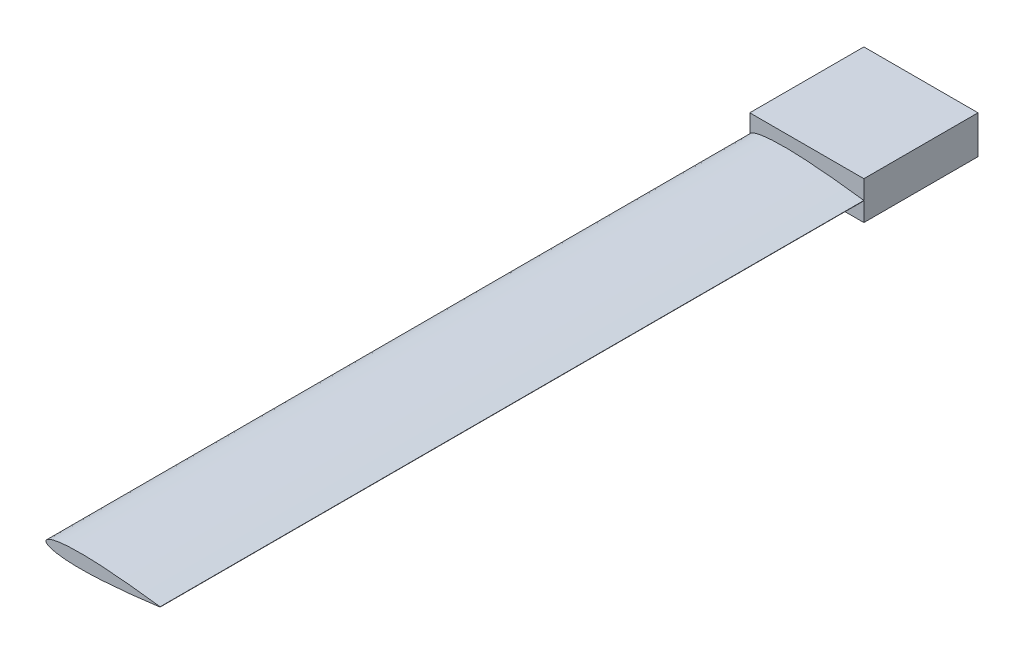
SolidWorks part; units mm, degrees
ref_plane "Front Plane" through (0, 0, 0) normal (0, 0, 1) x (1, 0, 0)
ref_plane "Top Plane" through (0, 0, 0) normal (0, 1, 0) x (1, 0, 0)
ref_plane "Right Plane" through (0, 0, 0) normal (1, 0, 0) x (0, 0, -1)
curve "Curve1"
  spline degree 3 poles (25.4, 0.032, 0) (25.3951, 0.0327, 0) (25.3753, 0.0355, 0) (25.3309, 0.0417, 0) (25.257, 0.052, 0) (25.1537, 0.0664, 0) (25.0214, 0.0846, 0) (24.8603, 0.1068, 0) (24.6708, 0.1326, 0) (24.4533, 0.1619, 0) (24.2084, 0.1946, 0) (23.9366, 0.2304, 0) (23.6385, 0.2691, 0) (23.3149, 0.3106, 0) (22.9666, 0.3545, 0) (22.5942, 0.4008, 0) (22.1987, 0.449, 0) (21.7811, 0.499, 0) (21.3422, 0.5505, 0) (20.8832, 0.6032, 0) (20.405, 0.6571, 0) (19.9089, 0.7116, 0) (19.3959, 0.7667, 0) (18.8673, 0.8219, 0) (18.3242, 0.8772, 0) (17.7681, 0.9321, 0) (17.2001, 0.9864, 0) (16.6216, 1.0399, 0) (16.0339, 1.0922, 0) (15.4384, 1.143, 0) (14.8366, 1.1921, 0) (14.2297, 1.2391, 0) (13.6193, 1.2836, 0) (13.0067, 1.3254, 0) (12.3935, 1.3642, 0) (11.7809, 1.3995, 0) (11.1705, 1.4311, 0) (10.5636, 1.4587, 0) (9.9618, 1.4818, 0) (9.3663, 1.5004, 0) (8.7786, 1.514, 0) (8.2001, 1.5224, 0) (7.632, 1.5254, 0) (7.0758, 1.5227, 0) (6.5327, 1.5144, 0) (6.0041, 1.5, 0) (5.491, 1.4798, 0) (4.9948, 1.4535, 0) (4.5166, 1.4212, 0) (4.0575, 1.3829, 0) (3.6185, 1.3388, 0) (3.2008, 1.2888, 0) (2.8052, 1.2334, 0) (2.4327, 1.1725, 0) (2.0841, 1.1064, 0) (1.7603, 1.0355, 0) (1.462, 0.96, 0) (1.1898, 0.8801, 0) (0.9445, 0.7962, 0) (0.7264, 0.7086, 0) (0.536, 0.6175, 0) (0.3737, 0.523, 0) (0.2396, 0.4254, 0) (0.1341, 0.3245, 0) (0.0574, 0.22, 0) (0.0105, 0.1114, 0) (-0.0051, 0, 0) (0.0105, -0.1114, 0) (0.0574, -0.22, 0) (0.1341, -0.3245, 0) (0.2396, -0.4254, 0) (0.3737, -0.523, 0) (0.536, -0.6175, 0) (0.7264, -0.7086, 0) (0.9445, -0.7962, 0) (1.1898, -0.8801, 0) (1.462, -0.96, 0) (1.7603, -1.0355, 0) (2.0841, -1.1064, 0) (2.4327, -1.1725, 0) (2.8052, -1.2334, 0) (3.2008, -1.2888, 0) (3.6185, -1.3388, 0) (4.0575, -1.3829, 0) (4.5166, -1.4212, 0) (4.9948, -1.4535, 0) (5.491, -1.4798, 0) (6.0041, -1.5, 0) (6.5327, -1.5144, 0) (7.0758, -1.5227, 0) (7.632, -1.5254, 0) (8.2001, -1.5224, 0) (8.7786, -1.514, 0) (9.3663, -1.5004, 0) (9.9618, -1.4818, 0) (10.5636, -1.4587, 0) (11.1705, -1.4311, 0) (11.7809, -1.3995, 0) (12.3935, -1.3642, 0) (13.0067, -1.3254, 0) (13.6193, -1.2836, 0) (14.2297, -1.2391, 0) (14.8366, -1.1921, 0) (15.4384, -1.143, 0) (16.0339, -1.0922, 0) (16.6216, -1.0399, 0) (17.2001, -0.9864, 0) (17.7681, -0.9321, 0) (18.3242, -0.8772, 0) (18.8673, -0.8219, 0) (19.3959, -0.7667, 0) (19.9089, -0.7116, 0) (20.405, -0.6571, 0) (20.8832, -0.6032, 0) (21.3422, -0.5505, 0) (21.7811, -0.499, 0) (22.1987, -0.449, 0) (22.5942, -0.4008, 0) (22.9666, -0.3545, 0) (23.3149, -0.3106, 0) (23.6385, -0.2691, 0) (23.9366, -0.2304, 0) (24.2084, -0.1946, 0) (24.4533, -0.1619, 0) (24.6708, -0.1326, 0) (24.8603, -0.1068, 0) (25.0214, -0.0846, 0) (25.1537, -0.0664, 0) (25.257, -0.052, 0) (25.3309, -0.0417, 0) (25.3753, -0.0355, 0) (25.3951, -0.0327, 0) (25.4, -0.032, 0) knots 0 0 0 0 0.000289 0.001156 0.002598 0.004612 0.007194 0.010336 0.014031 0.018272 0.023046 0.028343 0.03415 0.040454 0.047238 0.054489 0.062187 0.070314 0.078852 0.08778 0.097078 0.106722 0.116691 0.126961 0.137507 0.148306 0.159331 0.170556 0.181957 0.193504 0.205171 0.216932 0.228758 0.240621 0.252495 0.26435 0.276161 0.287898 0.299536 0.311047 0.322405 0.333584 0.344559 0.355306 0.3658 0.376018 0.385937 0.395538 0.404798 0.413699 0.422221 0.430349 0.438066 0.445357 0.452209 0.458612 0.464554 0.47003 0.475035 0.479569 0.483637 0.48725 0.490431 0.493219 0.495674 0.497891 0.5 0.502109 0.504326 0.506781 0.509569 0.51275 0.516363 0.520431 0.524965 0.52997 0.535446 0.541388 0.547791 0.554643 0.561934 0.569651 0.577779 0.586301 0.595202 0.604462 0.614063 0.623982 0.6342 0.644694 0.655441 0.666416 0.677595 0.688953 0.700464 0.712102 0.723839 0.73565 0.747505 0.759379 0.771242 0.783068 0.794829 0.806496 0.818043 0.829444 0.840669 0.851694 0.862493 0.873039 0.883309 0.893278 0.902922 0.91222 0.921148 0.929686 0.937813 0.945511 0.952762 0.959546 0.96585 0.971657 0.976954 0.981728 0.985969 0.989664 0.992806 0.995388 0.997402 0.998844 0.999711 1 1 1 1
sketch "Sketch2" plane through (0, 0, 0) normal (0, 0, 1) x (1, 0, 0)
  line L0 (25.2718, 0.0377) -> (25.2718, -0.0379)
  line L1 (25.2718, -0.0001) -> (-4.7282, -0.0001) construction
  line L2 (-4.7282, -0.0001) -> (-4.7282, 9.0074) construction
  spline S1 degree 3 poles (25.2718, 0.0377) (25.2659, 0.0385) (25.2426, 0.0418) (25.1495, 0.0548) (25.01, 0.0743) (24.8246, 0.0999) (24.6343, 0.1261) (24.4105, 0.1565) (24.1536, 0.1911) (23.8643, 0.2297) (23.5433, 0.272) (23.1913, 0.3178) (22.8091, 0.3667) (22.2419, 0.4383) (21.6376, 0.5126) (20.9975, 0.5892) (20.4792, 0.6501) (19.937, 0.7124) (19.3722, 0.776) (18.7862, 0.8404) (18.1803, 0.9054) (17.556, 0.9706) (16.9146, 1.0359) (16.2577, 1.1008) (15.5868, 1.165) (14.9036, 1.2281) (14.2094, 1.29) (13.5061, 1.35) (12.7953, 1.4079) (12.0785, 1.4634) (11.3576, 1.516) (10.6341, 1.5654) (9.9097, 1.6112) (8.9473, 1.6667) (7.9892, 1.7135) (6.8062, 1.759) (5.8749, 1.7847) (4.9569, 1.798) (4.286, 1.8015) (3.6291, 1.7984) (2.9876, 1.7886) (2.3632, 1.7716) (1.7573, 1.7477) (1.1712, 1.7166) (0.6064, 1.6785) (0.0641, 1.6333) (-0.4544, 1.5811) (-0.9478, 1.5222) (-1.415, 1.4567) (-1.855, 1.3847) (-2.2666, 1.3067) (-2.6491, 1.223) (-3.0014, 1.1338) (-3.3229, 1.0394) (-3.6127, 0.9404) (-3.8703, 0.8368) (-4.0952, 0.7292) (-4.2869, 0.6176) (-4.4452, 0.5024) (-4.5698, 0.3832) (-4.6604, 0.2598) (-4.7158, 0.1315) (-4.7342, -0.0001) (-4.7158, -0.1317) (-4.6604, -0.2599) (-4.5698, -0.3834) (-4.4452, -0.5025) (-4.2869, -0.6178) (-4.0952, -0.7294) (-3.8703, -0.837) (-3.6127, -0.9405) (-3.3229, -1.0396) (-3.0014, -1.1339) (-2.6491, -1.2232) (-2.2666, -1.3069) (-1.855, -1.3849) (-1.415, -1.4568) (-0.9478, -1.5223) (-0.4544, -1.5813) (0.0641, -1.6335) (0.6064, -1.6787) (1.1712, -1.7168) (1.7573, -1.7479) (2.3632, -1.7718) (2.9876, -1.7887) (3.6291, -1.7986) (4.286, -1.8017) (4.9569, -1.7982) (5.8749, -1.7848) (7.0455, -1.7526) (8.2283, -1.7026) (9.1862, -1.653) (9.9097, -1.6113) (10.6341, -1.5656) (11.3576, -1.5162) (12.0785, -1.4636) (12.7953, -1.4081) (13.5061, -1.3501) (14.2094, -1.2901) (14.9036, -1.2283) (15.5868, -1.1652) (16.2577, -1.101) (16.9146, -1.0361) (17.556, -0.9708) (18.1803, -0.9056) (18.7862, -0.8405) (19.3722, -0.7761) (19.937, -0.7126) (20.4792, -0.6503) (20.9975, -0.5894) (21.6376, -0.5128) (22.2419, -0.4385) (22.8091, -0.3669) (23.1913, -0.318) (23.5433, -0.2722) (23.8643, -0.2299) (24.1536, -0.1913) (24.4105, -0.1567) (24.6343, -0.1262) (24.8246, -0.1001) (25.01, -0.0745) (25.1495, -0.055) (25.2426, -0.042) (25.2659, -0.0387) (25.2718, -0.0379) knots 0 0 0 0 0.000289 0.001156 0.004612 0.007194 0.010336 0.014031 0.018272 0.023046 0.028343 0.03415 0.040454 0.047238 0.062187 0.070314 0.078852 0.08778 0.097078 0.106722 0.116691 0.126961 0.137507 0.148306 0.159331 0.170556 0.181957 0.193504 0.205171 0.216932 0.228758 0.240621 0.252495 0.26435 0.287898 0.299536 0.322405 0.333584 0.344559 0.355306 0.3658 0.376018 0.385937 0.395538 0.404798 0.413699 0.422221 0.430349 0.438066 0.445357 0.452209 0.458612 0.464554 0.47003 0.475035 0.479569 0.483637 0.48725 0.490431 0.493219 0.495674 0.497891 0.5 0.502109 0.504326 0.506781 0.509569 0.51275 0.516363 0.520431 0.524965 0.52997 0.535446 0.541388 0.547791 0.554643 0.561934 0.569651 0.577779 0.586301 0.595202 0.604462 0.614063 0.623982 0.6342 0.644694 0.655441 0.666416 0.677595 0.700464 0.723839 0.73565 0.747505 0.759379 0.771242 0.783068 0.794829 0.806496 0.818043 0.829444 0.840669 0.851694 0.862493 0.873039 0.883309 0.893278 0.902922 0.91222 0.921148 0.929686 0.937813 0.952762 0.959546 0.96585 0.971657 0.976954 0.981728 0.985969 0.989664 0.992806 0.995388 0.998844 0.999711 1 1 1 1
  point P4 (-3.1056, 8.5531)
  dimension "D1" = 30
extrude "Boss-Extrude1" add sketch "Sketch2" along normal blind 215
sketch "Sketch3" plane through (0, 0, 0) normal (0, 1, 0) x (1, 0, 0)
  line L0 (-4.7282, 0) -> (25.2718, 0)
  line L1 (25.2718, 0) -> (25.2718, -30)
  line L2 (25.2718, -215) -> (25.2718, 0) construction
  line L3 (25.2718, -30) -> (-4.7282, -30)
  line L4 (-4.7282, 0) -> (-4.7282, -215) construction
  line L5 (-4.7282, -30) -> (-4.7282, 0)
  dimension "D1" = 30
extrude "Boss-Extrude2" add sketch "Sketch3" along normal blind 5 and the other way blind 5
ref_plane "Plane1" through (0, 10, 0) normal (0, 1, 0) x (1, 0, 0)
equation "\"fuse_diam\"= 0.07"
equation "\"fuse_rad\"= 0.035"
equation "\"battery_length\"= 0.076"
equation "\"battery_width\"= 0.034"
equation "\"battery_height\"= 0.051"
equation "\"bat_bay_length\"= 0.096"
equation "\"wing_shelf\"= 0.0175"
equation "\"shell\"= 0.002"
equation "\"chord_length\"= 0.089"
equation "\"tail_length\"= 0.26532000000000006"
equation "\"tail_diam\"= 0.035"
equation "\"connector\"= 0.06633000000000001"
